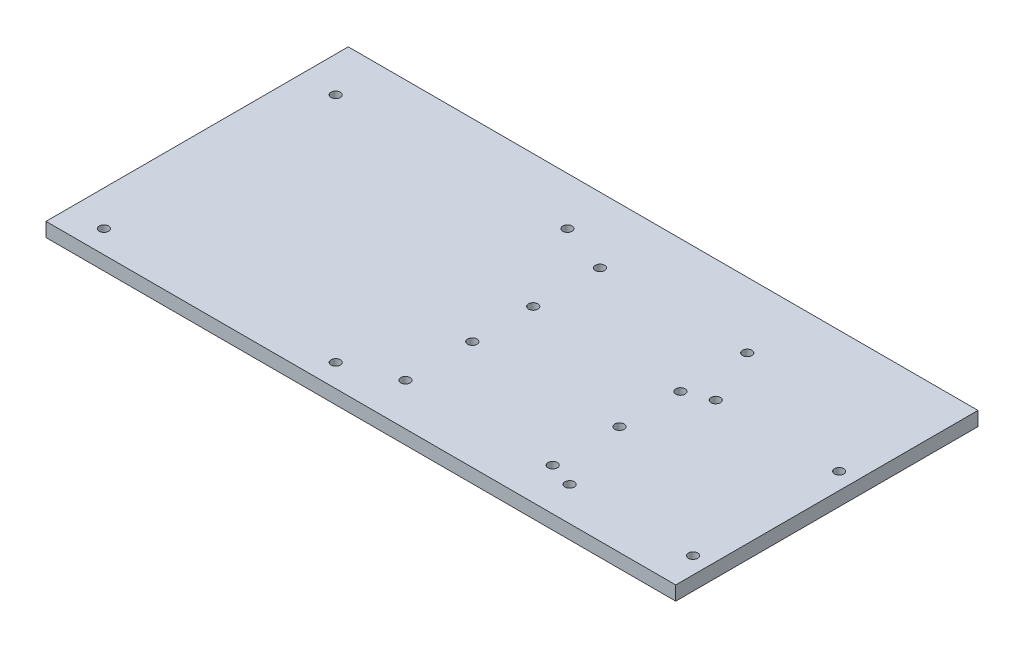
SolidWorks part; units mm, degrees
ref_plane "Front Plane" through (0, 0, 0) normal (0, 0, 1) x (1, 0, 0)
ref_plane "Top Plane" through (0, 0, 0) normal (0, 1, 0) x (1, 0, 0)
ref_plane "Right Plane" through (0, 0, 0) normal (1, 0, 0) x (0, 0, -1)
sketch "Sketch1" plane through (0, 0, 0) normal (0, 1, 0) x (1, 0, 0)
  line L1 (-125, -60) -> (125, -60)
  line L2 (-125, -60) -> (-125, 60)
  line L3 (-125, 60) -> (125, 60)
  line L4 (125, -60) -> (125, 60)
  line L5 (-125, -60) -> (125, 60) construction
  line L6 (-125, 60) -> (125, -60) construction
  point P0 (0, 0)
  dimension "D1" = 120
  dimension "D2" = 250
extrude "Boss-Extrude1" add sketch "Sketch1" along normal blind 5.588
hole_wizard "Ø3.0mm Clearance Dowel Hole2" positions "Sketch4" profile "Sketch5" hole size "Ø3.0" standard "ANSI Metric" end condition through all
sketch "Sketch4" plane through (-44.961, 0, -163.6882) normal (0, -1, 0) x (-1, 0, 0)
  point P0 (-45.936, -156.2482)
  point P3 (-25.961, -122.6882)
  point P6 (-45.936, -129.7282)
  point P9 (-45.936, -180.4282)
  point P12 (-45.936, -206.9482)
  point P15 (-25.961, -214.6882)
  point P18 (66.039, -214.6882)
  point P51 (-104.386, -206.9482)
  point P54 (-104.386, -180.4282)
  point P57 (-104.386, -156.2482)
  point P60 (-104.386, -129.7282)
  point P63 (-163.3388, -210.1882)
  point P66 (-163.3388, -152.1882)
  point P69 (-114.3388, -152.1882)
  point P72 (-114.3388, -210.1882)
  point P81 (66.039, -122.6882)
sketch "Sketch5" plane through (0.975, 0, -7.44) normal (1, 0, 0) x (0, 0, -1)
  line L0 (0, 0) -> (0, 5.588)
  line L1 (0, 5.588) -> (1.85, 5.588)
  line L2 (1.85, 5.588) -> (1.85, 0)
  line L3 (1.85, 0) -> (0, 0)
  line L4 (0, -6.35) -> (0, 107.95) construction
  dimension "Thru Hole Dia." = 3.7
  dimension "Thru Hole Depth" = 5.588
